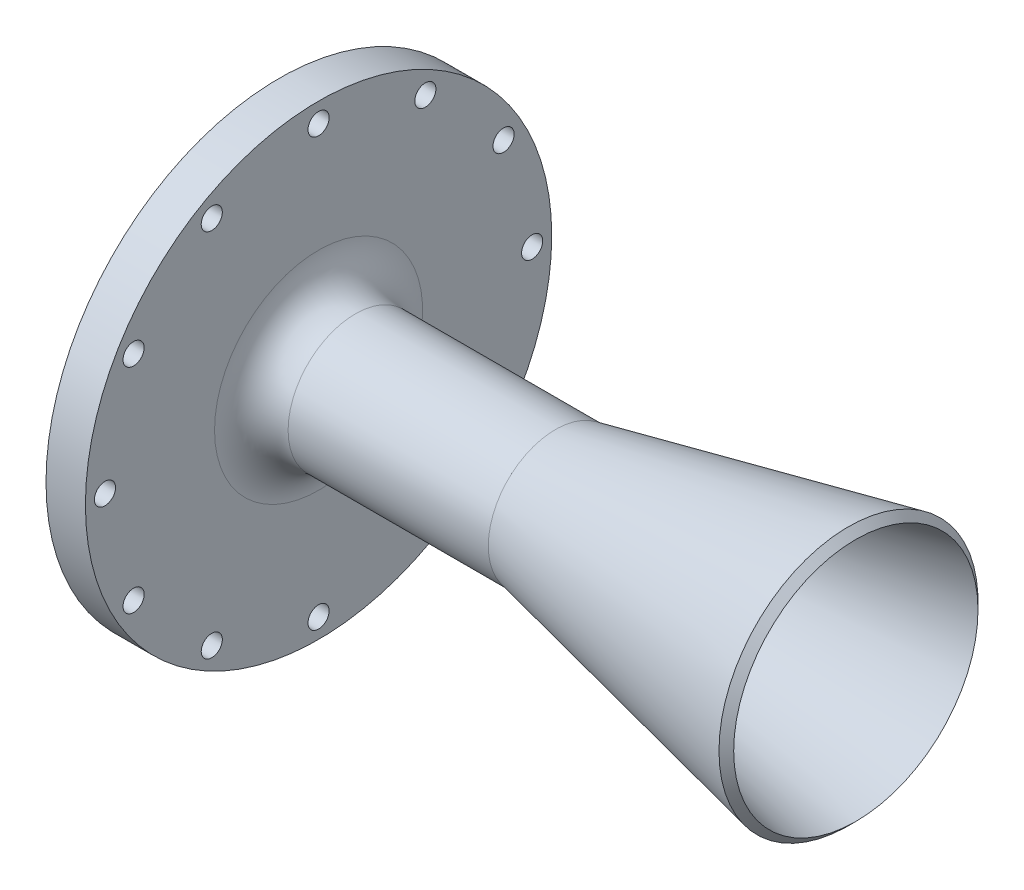
SolidWorks part; units mm, degrees
material "Stainless Steel (ferritic)"
ref_plane "Front Plane" through (0, 0, 0) normal (0, 0, 1) x (1, 0, 0)
ref_plane "Top Plane" through (0, 0, 0) normal (0, 1, 0) x (1, 0, 0)
ref_plane "Right Plane" through (0, 0, 0) normal (1, 0, 0) x (0, 0, -1)
sketch "Sketch2" plane through (0, 0, 0) normal (0, 0, 1) x (1, 0, 0)
  line L0 (0, 0) -> (165.0115, 0) construction
  line L1 (0, 20.5835) -> (0, 56.3562)
  line L2 (0, 56.3562) -> (9.525, 56.3562)
  line L3 (9.525, 56.3562) -> (9.525, 16.256)
  line L11 (66.8065, 16.256) -> (139.7, 31.75)
  line L17 (139.7, 31.75) -> (139.7, 29.5925)
  line L18 (60.325, 12.7208) -> (60.325, 14.351)
  line L19 (60.325, 14.351) -> (10.795, 14.351)
  line L20 (0, 20.5835) -> (10.795, 14.351)
  line L21 (60.325, 12.7208) -> (139.7, 29.5925)
  line L22 (9.525, 16.256) -> (66.8065, 16.256)
  dimension "D2" = 9.525
  dimension "D3" = 1.905
  dimension "D4" = 10.795
  dimension "D5" = 14.351
  dimension "D6" = 31.75
  dimension "D7" = 12
  dimension "D8" = 139.7
  dimension "D9" = 1.6302
  dimension "D10" = 30
  dimension "D11" = 56.3562
  dimension "D12" = 49.53
revolve "Main Structure" add sketch "Sketch2" angle 360 about L0
sketch "Sketch4" plane through (0, 0, 0) normal (-1, 0, 0) x (0, 0, 1)
  circle A0 centre (0, 0) radius 51.6255 construction
  circle A1 centre (0, -51.6255) radius 2.146
  circle A2 centre (-25.8127, -44.709) radius 2.146
  circle A3 centre (-44.709, -25.8128) radius 2.146
  circle A4 centre (-51.6255, 0) radius 2.146
  circle A5 centre (-44.709, 25.8127) radius 2.146
  circle A6 centre (-25.8128, 44.709) radius 2.146
  circle A7 centre (0, 51.6255) radius 2.146
  circle A8 centre (25.8127, 44.709) radius 2.146
  circle A9 centre (44.709, 25.8128) radius 2.146
  circle A10 centre (51.6255, 0) radius 2.146
  circle A11 centre (44.709, -25.8127) radius 2.146
  circle A12 centre (25.8128, -44.709) radius 2.146
  point P29 (0, 0)
  dimension "D1" = 12
  dimension "D2" = 103.251
hole_wizard "Flange Holes" positions "Sketch7" profile "Sketch8" hole size "#7" standard "ANSI Inch" end condition up to next
sketch "Sketch7" plane through (0, 0, 0) normal (-1, 0, 0) x (0, 0, 1)
  point P0 (0, -51.6255)
  point P3 (-25.8127, -44.709)
  point P6 (-44.709, -25.8128)
  point P9 (-51.6255, 0)
  point P12 (-44.709, 25.8127)
  point P15 (-25.8128, 44.709)
  point P18 (0, 51.6255)
  point P21 (25.8127, 44.709)
  point P24 (44.709, 25.8128)
  point P27 (51.6255, 0)
  point P30 (44.709, -25.8127)
  point P33 (25.8128, -44.709)
sketch "Sketch8" plane through (0, -51.6255, 0) normal (0, 1, 0) x (0, 0, 1)
  line L0 (0, 0) -> (0, 9.525)
  line L1 (0, 9.525) -> (2.5527, 9.525)
  line L2 (2.5527, 9.525) -> (2.5527, 0)
  line L5 (2.5527, 0) -> (0, 0)
  line L11 (0, -6.35) -> (0, 107.95) construction
  dimension "Thru Hole Dia." = 5.1054
  dimension "Thru Hole Depth" = 9.525
sketch "Sketch9" plane through (0, 0, 0) normal (-1, 0, 0) x (0, 0, 1)
  line L0 (0, 0) -> (-67.6727, 18.1329) construction
  line L1 (0, 0) -> (-51.6255, 0) construction
  circle A0 centre (0, 0) radius 51.6255 construction
  circle A1 centre (-49.8664, 13.3617) radius 2.9451
  circle A2 centre (49.8664, -13.3617) radius 2.9451
  point P14 (0, 0)
  dimension "D1" = 15
  dimension "D2" = 2
hole_wizard "Dowel Holes" positions "Sketch10" profile "Sketch11" hole size "3/16" standard "ANSI Inch"
sketch "Sketch10" plane through (0, 0, 0) normal (-1, 0, 0) x (0, 0, 1)
  point P0 (49.8664, -13.3617)
  point P3 (-49.8664, 13.3617)
sketch "Sketch11" plane through (0, -13.3617, 49.8664) normal (0, 1, 0) x (0, 0, 1)
  line L0 (0, 0) -> (0, 7.7808)
  line L1 (0, 7.7808) -> (2.3812, 6.35)
  line L2 (2.3812, 6.35) -> (2.3812, 0)
  line L5 (2.3812, 0) -> (0, 0)
  line L10 (0, 7.7808) -> (-2.3812, 6.35) construction
  line L11 (0, -6.35) -> (0, 107.95) construction
  dimension "Hole Dia." = 4.7625
  dimension "Hole Depth" = 6.35
  dimension "Drill Angle" = 118
fillet "Fillet1" radius 8.89 1 edges at (9.525, 0, 16.256)
sketch "Sketch13" plane through (0, 0, 0) normal (0, 1, 0) x (1, 0, 0)
  line L0 (0, 36) -> (3.1496, 0)
  line L1 (0, 56.3562) -> (0, -56.3562) construction
  line L2 (3.1496, 0) -> (0, 0)
  line L3 (0, 0) -> (0, 36)
  dimension "D1" = 36
  dimension "D2" = 5
revolve "Cut-Revolve1" cut sketch "Sketch13" angle 360 about L2
chamfer "Chamfer1" distance 2.54 angle 45 1 edges at (139.7, 0, 31.75) first distance on face at (139.7, 0, 31.75)
sketch "Sketch14" plane through (0, 0, 0) normal (-1, 0, 0) x (0, 0, 1)
  circle A0 centre (0, 0) radius 44.7421
  circle A1 centre (0, 0) radius 46.6725
  dimension "D1" = 89.4842
  dimension "D2" = 1.9304
extrude "Cut-Extrude1" cut sketch "Sketch14" against normal blind 0.9652
